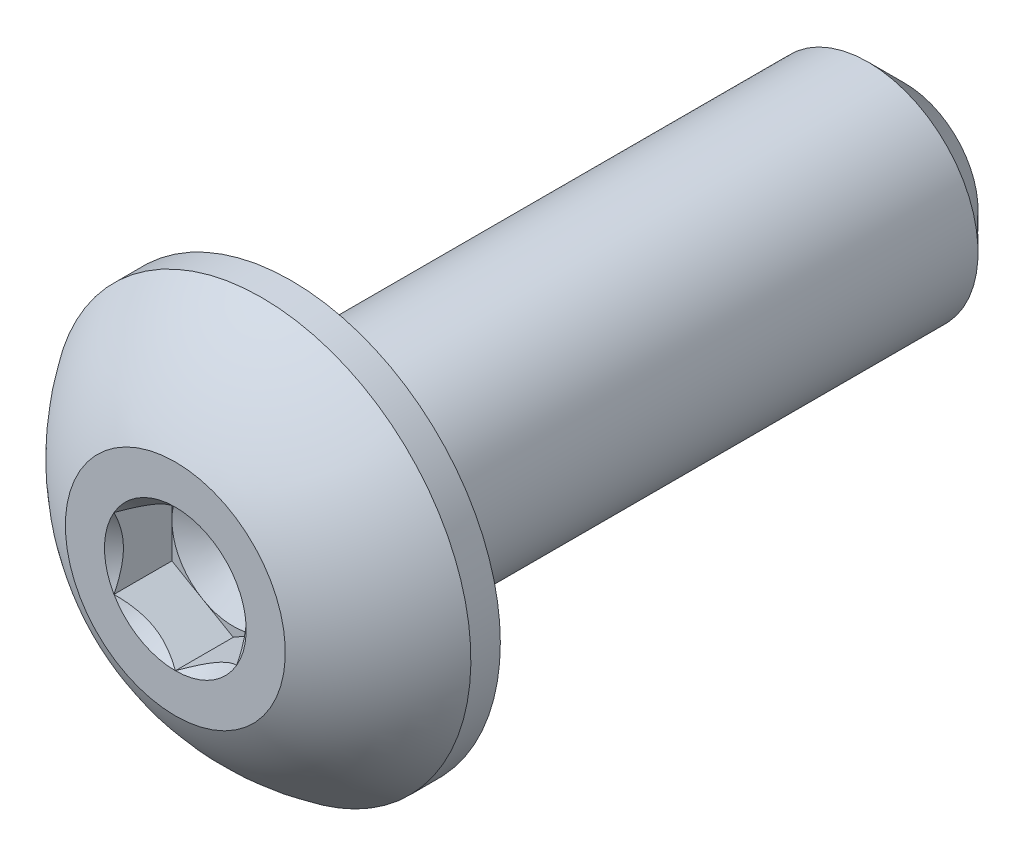
SolidWorks part; units mm, degrees
ref_plane "Front" through (0, 0, 0) normal (0, 0, 1) x (1, 0, 0)
ref_plane "Top" through (0, 0, 0) normal (0, 1, 0) x (1, 0, 0)
ref_plane "Right" through (0, 0, 0) normal (1, 0, 0) x (0, 0, -1)
sketch "Sketch1" plane through (0, 0, 0) normal (1, 0, 0) x (0, 0, -1)
  line L0 (0, 0) -> (-1.4986, 0) construction
  line L1 (0, 0) -> (7.9375, 0)
  line L2 (0, 0) -> (0, 1.4224)
  line L3 (0, 1.4224) -> (7.9375, 1.4224)
  line L4 (7.9375, 0) -> (7.9375, 1.4224)
  line L5 (0, -1.4224) -> (7.9375, -1.4224) construction
  dimension "D1" = 7.9375
  dimension "Thread Dia" = 2.8448
  dimension "Length" = 7.9375
  dimension "Head Height" = 1.4986
revolve "Revolve1" add sketch "Sketch1" angle 360 about L0
ref_plane "Plane1" through (0, 0, 1.4986) normal (0, 0, 1) x (1, 0, 0)
chamfer "Chamfer1" distance 0.4763 angle 45 1 edges at (0, 1.4224, -7.9375)
sketch "Sketch10" plane through (0, 0, 0) normal (1, 0, 0) x (0, 0, -1)
  line L0 (7.9375, 1.4224) -> (8.4931, 1.4224)
  line L1 (8.4931, 1.4224) -> (8.255, 1.01)
  line L2 (8.255, 1.01) -> (8.1756, 1.01)
  line L3 (8.1756, 1.01) -> (7.9375, 1.4224)
  line L4 (8.0566, 1.2162) -> (8.3741, 1.2162) construction
  dimension "D1" = 60
  dimension "D2" = 0.0794
  dimension "D3" = 0.3175
sketch "Sketch11" plane through (0, 0, -7.9375) normal (0, 0, -1) x (-1, 0, 0)
  circle A1 centre (0, 0) radius 0.9462
  circle A2 centre (0, 0) radius 0.9462
  dimension "D1" = 0
curve "Helix/Spiral1" pitch 0.635 height 11.1125 turns 17.5
sweep "Cut-Sweep1" [suppressed] cut profiles "Sketch10" path "Helix/Spiral1"
sketch "Sketch4" plane through (0, 0, 0) normal (0, 0, 1) x (1, 0, 0)
  circle A0 centre (0, 0) radius 2.7051
  dimension "Head Dia" = 5.4102
extrude "Extrude1" add sketch "Sketch4" along normal up to surface (1.4986 mm away) up to plane "Plane1"
sketch "Sketch9" plane through (0, 0, 0) normal (1, 0, 0) x (0, 0, -1)
  line L0 (0, 2.7051) -> (-0.381, 2.7051)
  line L1 (0, 2.7051) -> (0, 3.0861)
  line L2 (0, 3.0861) -> (-1.8796, 3.0861)
  line L3 (0, 0) -> (-1.4986, 0) construction
  line L4 (-1.8796, 3.0861) -> (-1.8796, 1.4224)
  line L5 (-1.8796, 1.4224) -> (-1.4986, 1.4224)
  line L6 (0, 0) -> (0, 1.4224) construction
  line L10 (0, 2.7051) -> (-1.4986, 2.7051) construction
  line L11 (0, 1.4224) -> (7.9375, 1.4224) construction
  line L12 (-1.4986, 2.7051) -> (-1.4986, -2.7051) construction
  arc A0 (-1.4986, 1.4224) -> (-0.381, 2.7051) centre (1.4288, 0) cw
  dimension "Side Head Height" = 0.381
revolve "Cut-Revolve3" cut sketch "Sketch9" angle 360 about L3
sketch "Sketch6" plane through (0, 0, 1.4986) normal (0, 0, 1) x (1, 0, 0)
  line L1 (0, -0.9165) -> (0.7937, -0.4583)
  line L2 (0.7937, -0.4583) -> (0.7937, 0.4583)
  line L3 (0.7937, 0.4583) -> (0, 0.9165)
  line L4 (0, 0.9165) -> (-0.7938, 0.4583)
  line L5 (-0.7938, 0.4583) -> (-0.7938, -0.4583)
  line L6 (-0.7938, -0.4583) -> (0, -0.9165)
  circle A0 centre (0, 0) radius 0.7938 construction
  dimension "Hex" = 1.5875
extrude "Cut-Extrude1" cut sketch "Sketch6" against normal blind 0.7493
sketch "Sketch7" plane through (0, 0, 1.4986) normal (0, 0, 1) x (1, 0, 0)
  circle A0 centre (0, 0) radius 0.9165
extrude "Cut-Extrude4" cut sketch "Sketch7" against normal blind 0.7493 draft 45
sketch "Sketch8" plane through (0, 0, 0.7493) normal (0, 0, 1) x (1, 0, 0)
  circle A0 centre (0, 0) radius 0.7938 construction
  circle A1 centre (0, 0) radius 0.7938
extrude "Cut-Extrude5" cut sketch "Sketch8" against normal blind 0.2498 draft 60
sketch "Sketch12" [suppressed] plane through (0, 0, 0) normal (1, 0, 0) x (0, 0, -1)
  line L1 (0, -1.4224) -> (7.9375, -1.4224) construction
  spline S0 degree 2 poles (7.4612, 0.013) (7.4194, 0.5945) (7.3819, 1.0058) (7.329, 1.5865) (7.276, 1.3739) (7.2231, 1.1614) (7.1702, 0.3681) (7.1173, -0.4251) (7.0644, -1.0058) (7.0115, -1.5865) (6.9585, -1.3739) (6.9056, -1.1614) (6.8527, -0.3681) (6.7998, 0.4251) (6.7469, 1.0058) (6.694, 1.5865) (6.641, 1.3739) (6.5881, 1.1614) (6.5352, 0.3681) (6.4823, -0.4251) (6.4294, -1.0058) (6.3765, -1.5865) (6.3235, -1.3739) (6.2706, -1.1614) (6.2177, -0.3681) (6.1648, 0.4251) (6.1119, 1.0058) (6.059, 1.5865) (6.006, 1.3739) (5.9531, 1.1614) (5.9002, 0.3681) (5.8473, -0.4251) (5.7944, -1.0058) (5.7415, -1.5865) (5.6885, -1.3739) (5.6356, -1.1614) (5.5827, -0.3681) (5.5298, 0.4251) (5.4769, 1.0058) (5.424, 1.5865) (5.371, 1.3739) (5.3181, 1.1614) (5.2652, 0.3681) (5.2123, -0.4251) (5.1594, -1.0058) (5.1065, -1.5865) (5.0535, -1.3739) (5.0006, -1.1614) (4.9477, -0.3681) (4.8948, 0.4251) (4.8419, 1.0058) (4.789, 1.5865) (4.736, 1.3739) (4.6831, 1.1614) (4.6302, 0.3681) (4.5773, -0.4251) (4.5244, -1.0058) (4.4715, -1.5865) (4.4185, -1.3739) (4.3656, -1.1614) (4.3127, -0.3681) (4.2598, 0.4251) (4.2069, 1.0058) (4.154, 1.5865) (4.101, 1.3739) (4.0481, 1.1614) (3.9952, 0.3681) (3.9423, -0.4251) (3.8894, -1.0058) (3.8365, -1.5865) (3.7835, -1.3739) (3.7306, -1.1614) (3.6777, -0.3681) (3.6248, 0.4251) (3.5719, 1.0058) (3.519, 1.5865) (3.466, 1.3739) (3.4131, 1.1614) (3.3602, 0.3681) (3.3073, -0.4251) (3.2544, -1.0058) (3.2015, -1.5865) (3.1485, -1.3739) (3.0956, -1.1614) (3.0427, -0.3681) (2.9898, 0.4251) (2.9369, 1.0058) (2.884, 1.5865) (2.831, 1.3739) (2.7781, 1.1614) (2.7252, 0.3681) (2.6723, -0.4251) (2.6194, -1.0058) (2.5665, -1.5865) (2.5135, -1.3739) (2.4606, -1.1614) (2.4077, -0.3681) (2.3548, 0.4251) (2.3019, 1.0058) (2.249, 1.5865) (2.196, 1.3739) (2.1431, 1.1614) (2.0902, 0.3681) (2.0373, -0.4251) (1.9844, -1.0058) (1.9315, -1.5865) (1.8785, -1.3739) (1.8256, -1.1614) (1.7727, -0.3681) (1.7198, 0.4251) (1.6669, 1.0058) (1.614, 1.5865) (1.561, 1.3739) (1.5081, 1.1614) (1.4552, 0.3681) (1.4023, -0.4251) (1.3494, -1.0058) (1.2965, -1.5865) (1.2435, -1.3739) (1.1906, -1.1614) (1.1377, -0.3681) (1.0848, 0.4251) (1.0319, 1.0058) (0.979, 1.5865) (0.926, 1.3739) (0.8731, 1.1614) (0.8202, 0.3681) (0.7673, -0.4251) (0.7144, -1.0058) (0.6615, -1.5865) (0.6085, -1.3739) (0.5556, -1.1614) (0.5027, -0.3681) (0.4498, 0.4251) (0.3969, 1.0058) (0.344, 1.5865) (0.291, 1.3739) (0.2381, 1.1614) (0.1852, 0.3681) (0.1323, -0.4251) (0.0794, -1.0058) (0.0419, -1.417) (0, -1.4223) knots 0.048731 0.048731 0.048731 0.055556 0.055556 0.064815 0.064815 0.074074 0.074074 0.083333 0.083333 0.092593 0.092593 0.101852 0.101852 0.111111 0.111111 0.12037 0.12037 0.12963 0.12963 0.138889 0.138889 0.148148 0.148148 0.157407 0.157407 0.166667 0.166667 0.175926 0.175926 0.185185 0.185185 0.194444 0.194444 0.203704 0.203704 0.212963 0.212963 0.222222 0.222222 0.231481 0.231481 0.240741 0.240741 0.25 0.25 0.259259 0.259259 0.268519 0.268519 0.277778 0.277778 0.287037 0.287037 0.296296 0.296296 0.305556 0.305556 0.314815 0.314815 0.324074 0.324074 0.333333 0.333333 0.342593 0.342593 0.351852 0.351852 0.361111 0.361111 0.37037 0.37037 0.37963 0.37963 0.388889 0.388889 0.398148 0.398148 0.407407 0.407407 0.416667 0.416667 0.425926 0.425926 0.435185 0.435185 0.444444 0.444444 0.453704 0.453704 0.462963 0.462963 0.472222 0.472222 0.481481 0.481481 0.490741 0.490741 0.5 0.5 0.509259 0.509259 0.518519 0.518519 0.527778 0.527778 0.537037 0.537037 0.546296 0.546296 0.555556 0.555556 0.564815 0.564815 0.574074 0.574074 0.583333 0.583333 0.592593 0.592593 0.601852 0.601852 0.611111 0.611111 0.62037 0.62037 0.62963 0.62963 0.638889 0.638889 0.648148 0.648148 0.657407 0.657407 0.666667 0.666667 0.675926 0.675926 0.685185 0.685185 0.694444 0.694444 0.701269 0.701269 0.701269 weights 0.948065 0.901259 1 0.866025 1 0.866025 1 0.866025 1 0.866025 1 0.866025 1 0.866025 1 0.866025 1 0.866025 1 0.866025 1 0.866025 1 0.866025 1 0.866025 1 0.866025 1 0.866025 1 0.866025 1 0.866025 1 0.866025 1 0.866025 1 0.866025 1 0.866025 1 0.866025 1 0.866025 1 0.866025 1 0.866025 1 0.866025 1 0.866025 1 0.866025 1 0.866025 1 0.866025 1 0.866025 1 0.866025 1 0.866025 1 0.866025 1 0.866025 1 0.866025 1 0.866025 1 0.866025 1 0.866025 1 0.866025 1 0.866025 1 0.866025 1 0.866025 1 0.866025 1 0.866025 1 0.866025 1 0.866025 1 0.866025 1 0.866025 1 0.866025 1 0.866025 1 0.866025 1 0.866025 1 0.866025 1 0.866025 1 0.866025 1 0.866025 1 0.866025 1 0.866025 1 0.866025 1 0.866025 1 0.866025 1 0.866025 1 0.866025 1 0.866025 1 0.866025 1 0.866025 1 0.866025 1 0.866025 1 0.866025 1 0.901259 0.948065 construction
  point P0 (6.9841, -1.4224)
equation "\"D1@Cut-Extrude1\"=\"Head Height@Sketch1\"/2"
equation "\"D1@Cut-Extrude4\"=\"D1@Cut-Extrude1\""
equation "\"D1@Cut-Extrude5\"=\"D1@Cut-Extrude1\"/3"
equation "\"D3@Helix/Spiral1\" = \"Length@Sketch1\" + .125"
equation "\"D1@Chamfer1\" = \"D4@Helix/Spiral1\" * .75"
equation "\"D2@Sketch10\" = \"D4@Helix/Spiral1\" * .125"
equation "\"D3@Sketch10\" = \"D4@Helix/Spiral1\" * .5"
